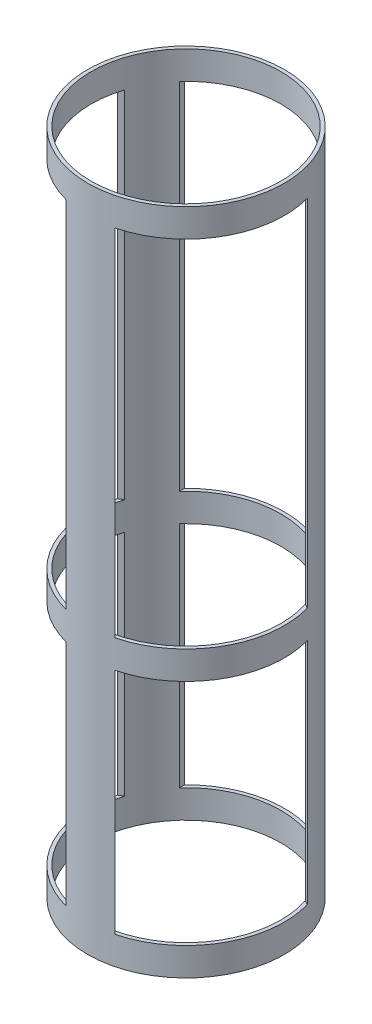
SolidWorks part; units mm, degrees
material "6061-T6 (SS)"
ref_plane "Front Plane" through (0, 0, 0) normal (0, 0, 1) x (1, 0, 0)
ref_plane "Top Plane" through (0, 0, 0) normal (0, 1, 0) x (1, 0, 0)
ref_plane "Right Plane" through (0, 0, 0) normal (1, 0, 0) x (0, 0, -1)
sketch "Sketch1" plane through (0, 0, 0) normal (0, 1, 0) x (1, 0, 0)
  circle A0 centre (0, 0) radius 88.9
  circle A1 centre (0, 0) radius 85.725
  dimension "D1" = 177.8
  dimension "D2" = 171.45
extrude "Boss-Extrude1" add sketch "Sketch1" along normal mid plane 603.25
sketch "Sketch2" plane through (0, 0, 0) normal (0, 0, 1) x (1, 0, 0)
  line L0 (88.9, -301.625) -> (88.9, 301.625) construction
  line L5 (-88.9, -301.625) -> (88.9, -301.625) construction
  line L6 (63.5, -276.225) -> (-63.5, -276.225)
  line L7 (-88.9, 301.625) -> (-88.9, -301.625) construction
  line L9 (63.5, -276.225) -> (63.5, -69.723)
  line L10 (63.5, -69.723) -> (-63.5, -69.723)
  line L11 (-63.5, -276.225) -> (-63.5, -69.723)
  line L12 (85.725, 301.625) -> (-85.725, 301.625) construction
  line L13 (63.5, -44.323) -> (-63.5, -44.323)
  line L14 (63.5, -44.323) -> (63.5, 276.225)
  line L15 (63.5, 276.225) -> (-63.5, 276.225)
  line L16 (-63.5, -44.323) -> (-63.5, 276.225)
  dimension "D1" = 25.4
  dimension "D2" = 25.4
  dimension "D3" = 25.4
  dimension "D4" = 231.902
  dimension "D5" = 25.4
  dimension "D6" = 25.4
extrude "Cut-Extrude1" cut sketch "Sketch2" against normal up to surface (62.217 mm away) up to face at (0, 301.625, 88.9)
pattern_circular "CirPattern1" count 3 over 360 about axis through (0, 301.625, 0) along (0, -1, 0) of "Cut-Extrude1"
ref_plane "Plane1" through (0, 0, 88.9) normal (0, 0, 1) x (1, 0, 0)
sketch "Sketch3" plane through (0, 0, 88.9) normal (0, 0, 1) x (1, 0, 0)
  line L0 (0, -97.79) -> (0, 97.79) construction
  line L1 (88.9, 301.625) -> (-88.9, 301.625) construction
  circle A0 centre (0, 295.275) radius 1.4351
  dimension "D1" = 2.8702
  dimension "D2" = 6.35
extrude "Cut-Extrude2" [suppressed] cut sketch "Sketch3" against normal blind 25.908
pattern_circular "CirPattern2" [suppressed] count 12 over 360 of bodies 104
mirror "Mirror1" [suppressed] about plane through (0, 0, 0) normal (0, 1, 0)
sketch "Sketch4" [suppressed] plane through (0, 0, 88.9) normal (0, 0, 1) x (1, 0, 0)
  line L0 (0, -97.79) -> (0, 97.79) construction
  circle A0 centre (0, -225.425) radius 1.4351
  circle A1 centre (0, -212.725) radius 1.4351
  circle A2 centre (0, -295.275) radius 1.4351 construction
  circle A3 centre (0, -149.225) radius 1.4351
  circle A4 centre (0, -136.525) radius 1.4351
  dimension "D1" = 69.85
  dimension "D2" = 2.8702
  dimension "D3" = 12.7
  dimension "D4" = 2.8702
  dimension "D5" = 63.5
  dimension "D6" = 12.7
  dimension "D7" = 2.8702
  dimension "D8" = 2.8702
extrude "Cut-Extrude3" [suppressed] cut sketch "Sketch4" against normal blind 34.798
pattern_circular "CirPattern3" [suppressed] count 3 over 360 reverse direction yes of bodies 107
sketch "Sketch5" [suppressed] plane through (0, 0, 88.9) normal (0, 0, 1) x (1, 0, 0)
  line L0 (0, -97.79) -> (0, 97.79) construction
  line L1 (63.5, -44.323) -> (-63.5, -44.323) construction
  circle A0 centre (0, -57.023) radius 1.4351
  circle A1 centre (0, 60.325) radius 1.4351
  circle A2 centre (0, 177.927) radius 1.4351
  circle A3 centre (0, 295.275) radius 1.4351 construction
  dimension "D1" = 2.8702
  dimension "D3" = 117.348
  dimension "D5" = 2.8702
  dimension "D6" = 2.8702
  dimension "D2" = 12.7
  dimension "D4" = 117.348
extrude "Cut-Extrude4" [suppressed] cut sketch "Sketch5" against normal blind 87.63
pattern_circular "CirPattern4" [suppressed] count 12 over 360 reverse direction yes of bodies 109
